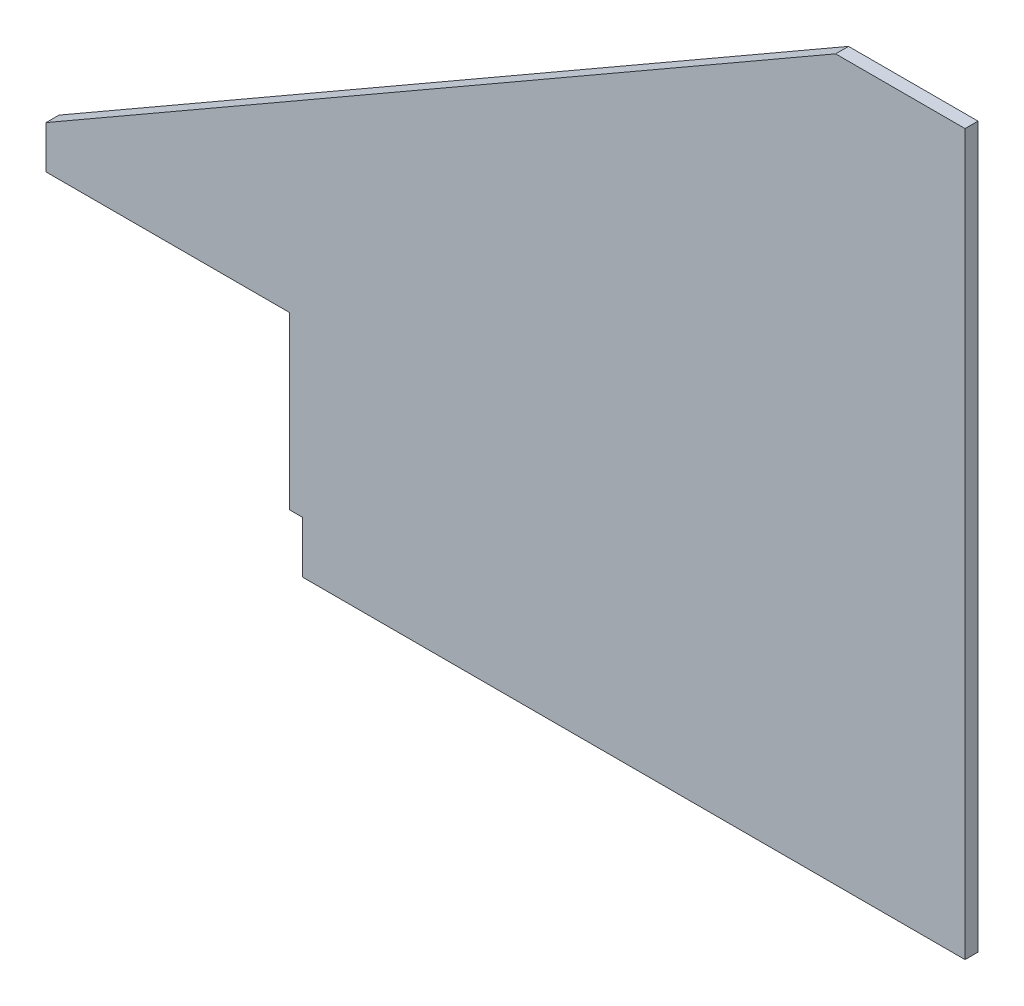
SolidWorks part; units mm, degrees
material "아크릴(내충격성)"
ref_plane "정면" through (0, 0, 0) normal (0, 0, 1) x (1, 0, 0)
ref_plane "윗면" through (0, 0, 0) normal (0, 1, 0) x (1, 0, 0)
ref_plane "우측면" through (0, 0, 0) normal (1, 0, 0) x (0, 0, -1)
sketch "스케치1" plane through (0, 0, 0) normal (0, 0, 1) x (1, 0, 0)
  line L0 (-128, -139) -> (128, -139)
  line L1 (128, -139) -> (128, 139)
  line L2 (128, 139) -> (78, 139)
  line L3 (78, 139) -> (-227, -36.4923)
  line L5 (-227, -53) -> (-227, -36.4923)
  line L7 (-128, -139) -> (-128, -119)
  line L8 (-133, -53) -> (-227, -53)
  line L14 (-128, -119) -> (-133, -119)
  line L17 (-133, -119) -> (-133, -53)
  point P3 (128, 0)
  point P6 (0, -139)
  dimension "D1" = 278
  dimension "D4" = 50
  dimension "D5" = 256
  dimension "D8" = 5
  dimension "D9" = 86
extrude "보스-돌출1" add sketch "스케치1" along normal blind 5 contours L3 L5 L8 L17 L14 L7 L0 L1 L2
